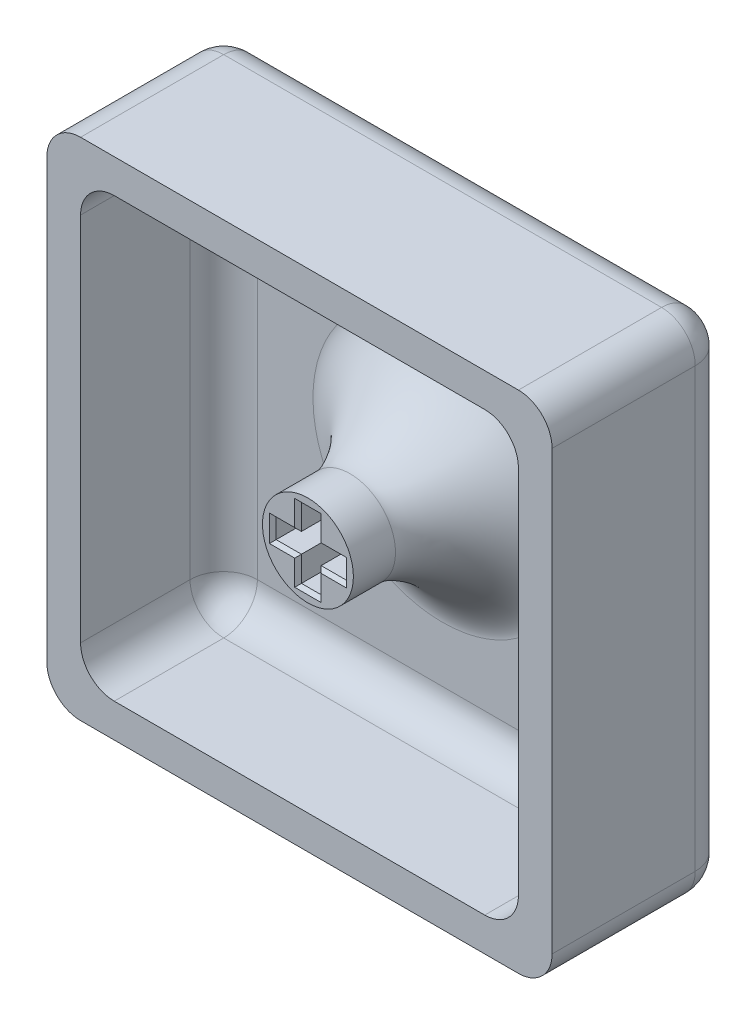
SolidWorks part; units mm, degrees
other "标注1"
sketch "草图2" plane through (15, -15, 10) normal (0.3933, -0.7926, 0.466) x (0.9059, 0.4207, -0.0491)
ref_plane "前视基准面" through (0, 0, 0) normal (0, 0, 1) x (1, 0, 0)
ref_plane "上视基准面" through (0, 0, 0) normal (0, 1, 0) x (1, 0, 0)
ref_plane "右视基准面" through (0, 0, 0) normal (1, 0, 0) x (0, 0, -1)
sketch "草图1" plane through (0, 0, 0) normal (0, 0, 1) x (1, 0, 0)
  line L0 (-13, 15) -> (13, 15)
  line L1 (-11, 13) -> (11, 13)
  line L2 (-13, 11) -> (-13, -11)
  line L3 (-11, -13) -> (11, -13)
  line L4 (13, 11) -> (13, -11)
  line L5 (0, -13) -> (0, 13) construction
  line L6 (-13, 0) -> (13, 0) construction
  line L7 (15, 13) -> (15, -13)
  line L8 (-13, -15) -> (13, -15)
  line L9 (-15, 13) -> (-15, -13)
  line L10 (-13, -13) -> (13, -13) construction
  line L11 (-2.085, 0.585) -> (2.085, 0.585)
  line L12 (-2.085, 0.585) -> (-2.085, -0.585)
  line L13 (-2.085, -0.585) -> (2.085, -0.585)
  line L14 (2.085, 0.585) -> (2.085, -0.585)
  line L15 (0, -0.585) -> (0, 0.585) construction
  line L16 (-2.085, 0) -> (2.085, 0) construction
  line L17 (-0.585, 2.085) -> (0.585, 2.085)
  line L18 (-0.585, 2.085) -> (-0.585, -2.085)
  line L19 (-0.585, -2.085) -> (0.585, -2.085)
  line L20 (0.585, 2.085) -> (0.585, -2.085)
  line L21 (0, -2.085) -> (0, 2.085) construction
  line L22 (-0.585, 0) -> (0.585, 0) construction
  line L23 (13, 13) -> (13, -13) construction
  line L24 (-13, 13) -> (13, 13) construction
  line L25 (-13, 13) -> (-13, -13) construction
  line L26 (-15, 15) -> (-15, -15) construction
  line L27 (-15, -15) -> (15, -15) construction
  line L28 (15, 15) -> (15, -15) construction
  line L29 (-15, 15) -> (15, 15) construction
  line L36 (-13, 0) -> (-2.5, 0) construction
  circle A0 centre (0, 0) radius 2.7
  arc A1 (11, -13) -> (13, -11) centre (11, -11) ccw
  arc A2 (13, 11) -> (11, 13) centre (11, 11) ccw
  arc A3 (-13, 11) -> (-11, 13) centre (-11, 11) cw
  arc A4 (-13, -11) -> (-11, -13) centre (-11, -11) ccw
  arc A5 (-15, -13) -> (-13, -15) centre (-13, -13) ccw
  arc A6 (13, -15) -> (15, -13) centre (13, -13) ccw
  arc A7 (15, 13) -> (13, 15) centre (13, 13) ccw
  arc A8 (-15, 13) -> (-13, 15) centre (-13, 13) cw
  point P0 (0, 0)
  point P19 (13, -13)
  point P66 (0.0162, 0.0162)
  dimension "D4" = 5.4
  dimension "D9" = 2
  dimension "D1" = 30
  dimension "D2" = 30
  dimension "D5" = 4.17
  dimension "D6" = 1.17
  dimension "D7" = 4.17
  dimension "D8" = 1.17
  dimension "D3" = 2
extrude "凸台-拉伸1" add sketch "草图1" along normal blind 8.5 contours A8 L9 A5 L8 A6 L7 A7 L0 A4 L2 A3 L1 A2 L4 A1 L3 region at (0, 14.5757, 0)
extrude "凸台-拉伸2" add sketch "草图1<6>" along normal blind 8 separate body contours A0 L17 L20 L11 L14 L13 L19 L18 L12 region at (-2.6236, 0, 0)
sketch "草图1<6>" plane through (0, 0, 0) normal (0, 0, 1) x (1, 0, 0) same geometry as "草图1"
extrude "凸台-拉伸3" add sketch "草图1<7>" against normal blind 2 contours L8 A6 L7 A7 L0 A8 L9 A5
sketch "草图1<7>" plane through (0, 0, 0) normal (0, 0, 1) x (1, 0, 0) same geometry as "草图1"
fillet "圆角1" radius 2 8 edges at (-14.4142, 14.4142, -2) (-15, 0, -2) (-14.4142, -14.4142, -2) (0, -15, -2) (14.4142, -14.4142, -2) (15, 0, -2) (14.4142, 14.4142, -2) (0, 15, -2)
chamfer "倒角1" distance 0.2 angle 45 12 edges at (-0.585, 1.335, 8) (-1.335, 0.585, 8) (-2.085, 0, 8) (-1.335, -0.585, 8) (-0.585, -1.335, 8) (0, -2.085, 8) (0.585, -1.335, 8) (1.335, -0.585, 8) (2.085, 0, 8) (1.335, 0.585, 8) (0.585, 1.335, 8) (0, 2.085, 8)
fillet "圆角2" radius 2 8 edges at (-12.4142, -12.4142, 0) (-13, 0, 0) (-12.4142, 12.4142, 0) (0, 13, 0) (12.4142, 12.4142, 0) (13, 0, 0) (12.4142, -12.4142, 0) (0, -13, 0)
fillet "圆角3" radius 5 1 edges at (2.7, 0, 0) second distance 5.5 conic rho 0.25 first distance on face at (0, 0, 0)
